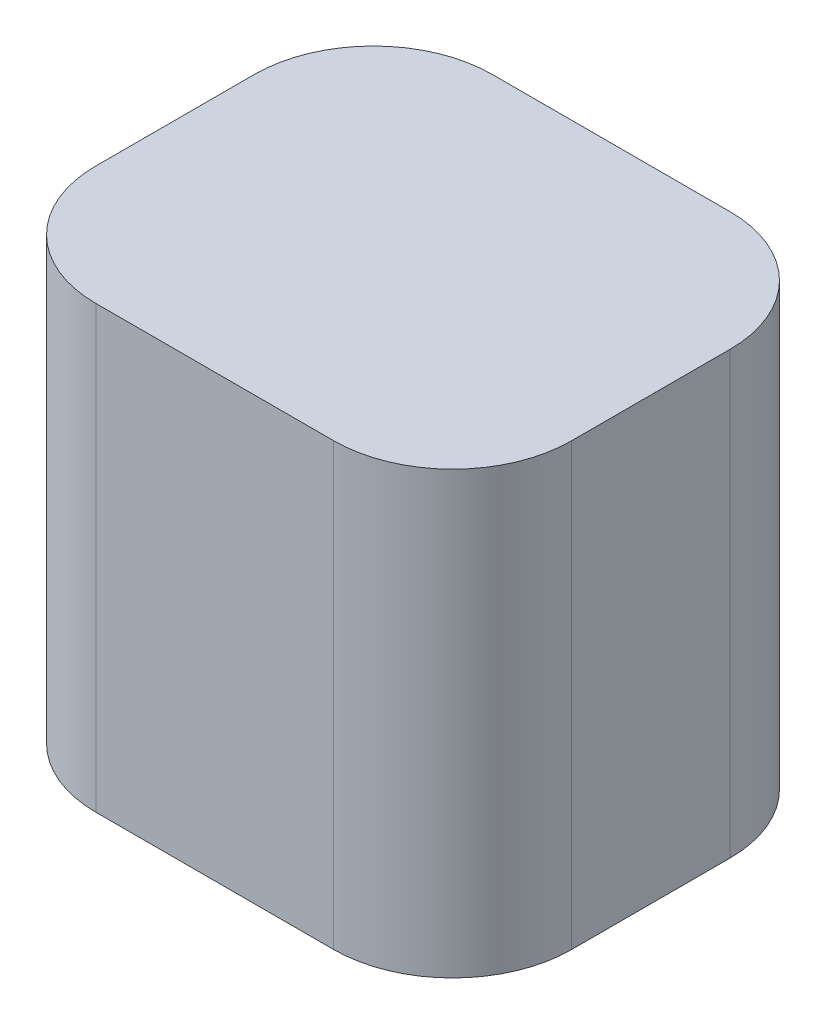
SolidWorks part; units mm, degrees
ref_plane "Front Plane" through (0, 0, 0) normal (0, 0, 1) x (1, 0, 0)
ref_plane "Top Plane" through (0, 0, 0) normal (0, 1, 0) x (1, 0, 0)
ref_plane "Right Plane" through (0, 0, 0) normal (1, 0, 0) x (0, 0, -1)
sketch "Sketch1" plane through (0, 0, 0) normal (0, 0, 1) x (1, 0, 0)
  line L4 (0, 0) -> (45, 0)
  line L5 (0, 0) -> (0, 11.1125)
  line L6 (0, 11.1125) -> (45, 11.1125) construction
  line L9 (15, 16.1125) -> (15, 11.1125) construction
  line L10 (30, 16.1125) -> (30, 11.1125) construction
  line L11 (0, 11.1125) -> (10, 11.1125)
  line L12 (35, 11.1125) -> (45, 11.1125)
  line L13 (45, 11.1125) -> (45, 0)
  spline S0 degree 3 poles (10, 11.1125) (14.5766, 20.182) (30.4234, 20.182) (35, 11.1125) knots 0 0 0 0 1 1 1 1
  dimension "D5" = 5
  dimension "D1" = 10
  dimension "D2" = 10
  dimension "D3" = 25
  dimension "D4" = 11.1125
  dimension "D6" = 5
  dimension "D7" = 5
extrude "Boss-Extrude1" add sketch "Sketch1" against normal blind 10
sketch "Sketch2" plane through (0, 0, 0) normal (0, 0, 1) x (1, 0, 0)
  line L0 (0, 0) -> (45, 0) construction
  line L2 (10, 11.1125) -> (10, 0) construction
  line L3 (10, 0) -> (35, 0) construction
  line L4 (35, 11.1125) -> (35, 0) construction
  line L5 (33, 10.6109) -> (33, 0)
  line L6 (12, 10.6109) -> (12, 0)
  spline S0 degree 3 poles (-1884.251, -531.3416) (2112.7694, 200.999) (-2067.7633, 201) (1929.2342, -531.3385) knots -3.992988 -3.992988 -3.992988 -3.992988 4.992976 4.992976 4.992976 4.992976 only from (35, 11.1125) to (10, 11.1125) construction
  spline S1 degree 3 poles (35, 11.1125) (30.4234, 20.182) (14.5766, 20.182) (10, 11.1125) knots 0 0 0 0 1 1 1 1 construction
  spline S2 degree 1 poles (33, 10.6109) (12, 10.6109) knots 0 0 1 1 construction
  spline S3 degree 3 poles (33, 10.6109) (32.5185, 11.4554) (31.2713, 12.9823) (27.9312, 15.2011) (22.5, 16.3903) (17.0688, 15.2011) (13.7287, 12.9823) (12.4815, 11.4554) (12, 10.6109) knots 0.018308 0.018308 0.018308 0.018308 0.138731 0.259154 0.5 0.740846 0.861269 0.981692 0.981692 0.981692 0.981692
  dimension "D1" = 2
extrude "Cut-Extrude2" cut sketch "Sketch2" against normal through all both and the other way through all
sketch "Sketch3" plane through (12, 0, 0) normal (1, 0, 0) x (0, 0, -1)
  line L0 (10, 10.6109) -> (0, 0) construction
  circle A0 centre (5, 5.3055) radius 2.5
  dimension "D1" = 5
extrude "Cut-Extrude3" cut sketch "Sketch3" against normal blind 6
sketch "Sketch4" plane through (6, 0, 0) normal (1, 0, 0) x (0, 0, -1)
  line L0 (2.5, 5.3055) -> (7.5, 5.3055) construction
  line L1 (5, 2.8055) -> (5, 7.8055) construction
  line L2 (5, 2.8055) -> (7.5, 2.8055) construction
  circle A0 centre (5, 5.3055) radius 2.5 construction
  circle A1 centre (5, 5.3055) radius 2
  dimension "D1" = 4
revolve "Cut-Revolve1" cut sketch "Sketch4" angle 90 about L2
sketch "Sketch5" plane through (0, 2.8055, 0) normal (0, 1, 0) x (1, 0, 0)
  circle A0 centre (3.5, 5) radius 2 construction
  circle A1 centre (3.5, 5) radius 2
extrude "Cut-Extrude4" cut sketch "Sketch5" against normal up to surface (2.8055 mm away) up to face at (6, 0, -5)
ref_plane "Plane1" through (22.5, 0, 0) normal (1, 0, 0) x (0, 0, -1)
mirror "Mirror1" about plane through (22.5, 0, 0) normal (1, 0, 0) of "Cut-Extrude4", "Cut-Revolve1", "Cut-Extrude3"
fillet "Fillet1" radius 5 4 edges at (10, 11.1125, -5) (35, 11.1125, -5) (33, 10.6109, -5) (12, 10.6109, -5)
sketch "Sketch6" plane through (0, 0, 0) normal (-1, 0, 0) x (0, 0, 1)
  line L0 (-10, 0) -> (0, 0)
  line L1 (-10, 0) -> (-10, 29.6855)
  line L2 (0, 0) -> (0, 29.6855)
  line L3 (-10, 29.6855) -> (0, 29.6855)
extrude "Cut-Extrude5" cut sketch "Sketch6" against normal up to surface (33 mm away) up to face at (33, 7.8055, -5)
sketch "Sketch7" plane through (0, 11.1125, 0) normal (0, 1, 0) x (1, 0, 0)
  line L1 (45, 0) -> (45, 10)
  line L2 (45, 0) -> (25.2323, 0)
  line L3 (45, 10) -> (25.2323, 10)
  line L4 (25.2323, 0) -> (25.2323, 10)
extrude "Cut-Extrude6" cut sketch "Sketch7" along normal through all
fillet "Fillet2" radius 3 4 edges at (33, 5.5563, -10) (45, 5.5562, 0) (33, 5.5563, 0) (45, 5.5562, -10)
